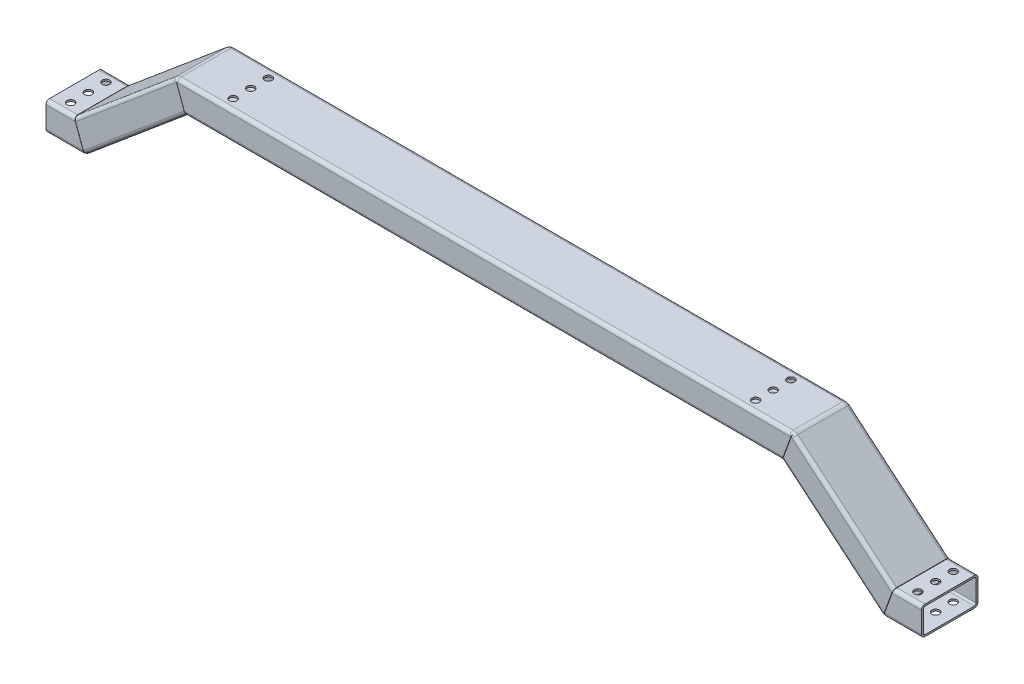
SolidWorks part; units mm, degrees
material "6061-T6 (SS)"
ref_plane "Front" through (0, 0, 0) normal (0, 0, 1) x (1, 0, 0)
ref_plane "Top" through (0, 0, 0) normal (0, 1, 0) x (1, 0, 0)
ref_plane "Right" through (0, 0, 0) normal (1, 0, 0) x (0, 0, -1)
sketch "Sketch1" plane through (0, 0, 0) normal (0, 0, 1) x (1, 0, 0)
  line L0 (272.866, 0) -> (-272.866, 0)
  line L1 (-272.866, 0) -> (-363.6776, -76.2)
  line L2 (-363.6776, -76.2) -> (-393.7, -76.2)
  line L3 (272.866, 0) -> (363.6776, -76.2)
  line L4 (363.6776, -76.2) -> (393.7, -76.2)
  line L5 (368.3, -63.5) -> (393.7, -63.5) construction
  line L6 (277.4884, 12.7) -> (368.3, -63.5) construction
  line L7 (277.4884, 12.7) -> (-277.4884, 12.7) construction
  line L8 (-277.4884, 12.7) -> (-368.3, -63.5) construction
  line L9 (-368.3, -63.5) -> (-393.7, -63.5) construction
  line L10 (359.0552, -88.9) -> (393.7, -88.9) construction
  line L11 (268.2435, -12.7) -> (359.0552, -88.9) construction
  line L12 (268.2435, -12.7) -> (-268.2435, -12.7) construction
  line L13 (-268.2435, -12.7) -> (-359.0552, -88.9) construction
  line L14 (-359.0552, -88.9) -> (-393.7, -88.9) construction
  line L15 (-359.0552, -88.9) -> (-393.7, -88.9) construction
  point P4 (0, 0)
  dimension "D1" = 12.7
  dimension "D3" = 25.4
  dimension "D4" = 76.2
  dimension "D5" = 40
  dimension "D6" = 787.4
  dimension "D2" = 12.7
ref_plane "Plane1" through (-393.7, 0, 0) normal (1, 0, 0) x (0, 0, -1)
sketch "Sketch2" plane through (-393.7, 0, 0) normal (1, 0, 0) x (0, 0, -1)
  line L1 (22.225, -88.9) -> (-22.225, -88.9)
  line L2 (25.4, -85.725) -> (25.4, -66.675)
  line L3 (22.225, -63.5) -> (-22.225, -63.5)
  line L4 (-25.4, -85.725) -> (-25.4, -66.675)
  line L5 (25.4, -88.9) -> (-25.4, -63.5) construction
  line L6 (25.4, -63.5) -> (-25.4, -88.9) construction
  arc A0 (-22.225, -88.9) -> (-25.4, -85.725) centre (-22.225, -85.725) cw
  arc A1 (22.225, -88.9) -> (25.4, -85.725) centre (22.225, -85.725) ccw
  arc A2 (25.4, -66.675) -> (22.225, -63.5) centre (22.225, -66.675) ccw
  arc A3 (-22.225, -63.5) -> (-25.4, -66.675) centre (-22.225, -66.675) ccw
  dimension "D3" = 3.175
  dimension "D1" = 25.4
  dimension "D2" = 50.8
sweep "Sweep-Thin1" add profiles "Sketch2" path "Sketch1" parameters "D1"=1.5875
fillet "Fillet1" radius 6.35 12 edges at (-277.1499, 11.7701, -24.4701) (-277.1499, 11.7701, 24.4701) (-359.3936, -87.9701, 24.4701) (-359.3936, -87.9701, -24.4701) (277.1499, 11.7701, -24.4701) (277.1499, 11.7701, 24.4701) (359.3936, -87.9701, 24.4701) (359.3936, -87.9701, -24.4701) (359.0552, -88.9, 0) (277.4884, 12.7, 0) (-359.0552, -88.9, 0) (-277.4884, 12.7, 0)
sketch "Sketch3" plane through (0, 0, 0) normal (0, 0, 1) x (1, 0, 0)
  line L0 (-379.656, -32.2997) -> (-359.633, -87.3125)
  line L1 (-367.1444, -66.675) -> (-368.3, -63.5) construction
  line L3 (-256.8875, -43.9003) -> (-276.9106, 11.1125)
  line L4 (-268.2435, -12.7) -> (-269.3991, -9.525) construction
  line L5 (268.2435, -12.7) -> (269.3991, -9.525) construction
  line L6 (276.9106, 11.1125) -> (256.8875, -43.9003)
  line L7 (379.656, -32.2997) -> (359.633, -87.3125)
  line L9 (367.1444, -66.675) -> (368.3, -63.5) construction
extrude "Cut-Extrude-Thin1" cut sketch "Sketch3" against normal through all both and the other way through all thin thin type mid plane wall 0.254
hole_wizard "1/4 Clearance Hole1" positions "Sketch4" profile "Sketch5" hole size "1/4" standard "ANSI Inch" end condition through all
sketch "Sketch4" plane through (0, 12.7, 0) normal (0, 1, 0) x (1, 0, 0)
  line L0 (-234.95, 15.875) -> (-234.95, -15.875) construction
  line L2 (-381, 15.875) -> (-381, -15.875) construction
  line L5 (-275.1772, 25.4) -> (275.1772, 25.4) construction
  line L6 (-275.1772, -25.4) -> (275.1772, -25.4) construction
  line L7 (-393.7, 22.225) -> (-393.7, -22.225) construction
  line L8 (0, 0) -> (0, 49.3534) construction
  point P0 (-234.95, 15.875)
  point P2 (-234.95, 0)
  point P4 (-234.95, -15.875)
  point P6 (-381, 15.875)
  point P8 (-381, 0)
  point P10 (-381, -15.875)
  point P35 (234.95, -15.875)
  point P36 (234.95, 0)
  point P37 (234.95, 15.875)
  point P38 (381, -15.875)
  point P39 (381, 0)
  point P40 (381, 15.875)
  dimension "D1" = 9.525
  dimension "D2" = 9.525
  dimension "D3" = 12.7
  dimension "D4" = 469.9
sketch "Sketch5" plane through (-234.95, 12.7, -15.875) normal (1, 0, 0) x (0, 0, 1)
  line L0 (0, 0) -> (0, 101.6)
  line L1 (0, 101.6) -> (3.3782, 101.6)
  line L2 (3.3782, 101.6) -> (3.3782, 0)
  line L5 (3.3782, 0) -> (0, 0)
  line L11 (0, -6.35) -> (0, 107.95) construction
  dimension "Thru Hole Dia." = 6.7564
  dimension "Thru Hole Depth" = 101.6
